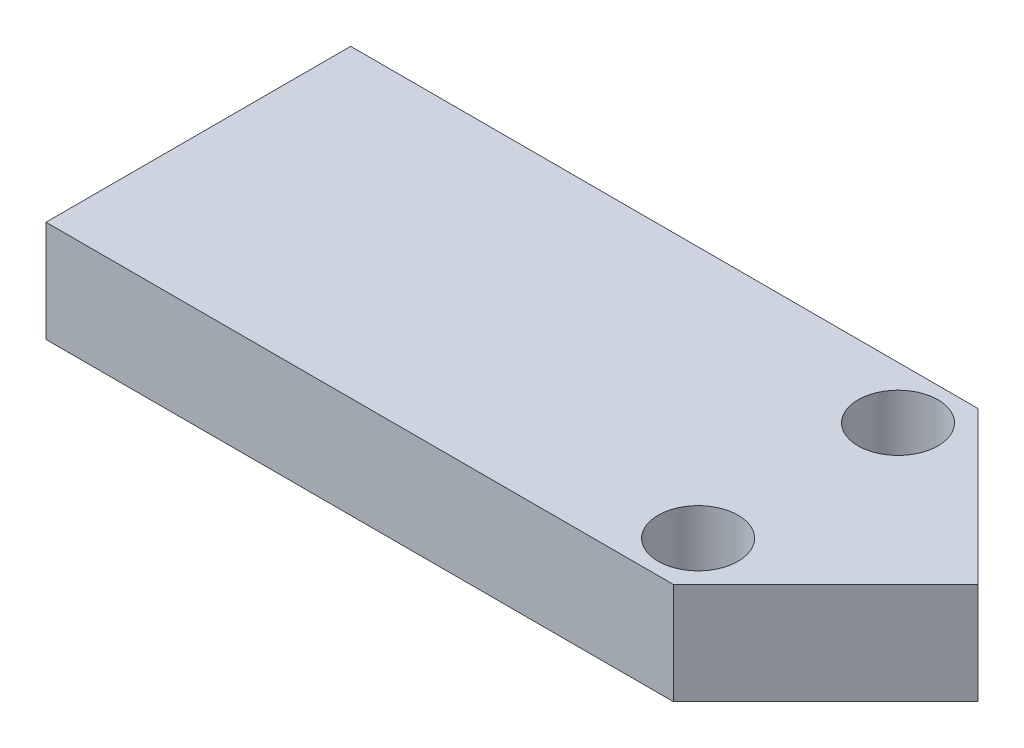
SolidWorks part; units mm, degrees
ref_plane "Front Plane" through (0, 0, 0) normal (0, 0, 1) x (1, 0, 0)
ref_plane "Top Plane" through (0, 0, 0) normal (0, 1, 0) x (1, 0, 0)
ref_plane "Right Plane" through (0, 0, 0) normal (1, 0, 0) x (0, 0, -1)
sketch "Sketch1" plane through (0, 0, 0) normal (0, 1, 0) x (1, 0, 0)
  line L0 (156.9, 76.2) -> (195, 38.1)
  line L1 (0, 0) -> (156.9, 0)
  line L2 (0, 0) -> (0, 76.2)
  line L3 (0, 76.2) -> (156.9, 76.2)
  line L4 (156.9, 0) -> (156.9, 76.2)
  line L5 (195, 38.1) -> (156.9, 0)
  line L6 (0, 38.1) -> (195, 38.1)
  dimension "D1" = 76.2
  dimension "D2" = 195
extrude "Boss-Extrude1" add sketch "Sketch1" along normal blind 25.4 contours L6 L2 L1 L4 | L6 L4 L5 | L4 L6 L0 | L2 L6 L4 L3 region at (78.45, 0, -57.15) region at (169.6, 0, -50.8) region at (169.6, 0, -25.4) region at (78.45, 0, -19.05)
sketch "Sketch2" plane through (0, 25.4, 0) normal (0, 1, 0) x (1, 0, 0)
  line L0 (195, 38.1) -> (150, 38.1)
  line L1 (150, 38.1) -> (150, 13.1)
  line L2 (150, 38.1) -> (150, 63.1)
  circle A0 centre (150, 63.1) radius 10
  circle A1 centre (150, 13.1) radius 10
  dimension "D1" = 45
  dimension "D2" = 25
  dimension "D3" = 25
extrude "Cut-Extrude1" cut sketch "Sketch2" against normal blind 25.4 contours A0 | A1
